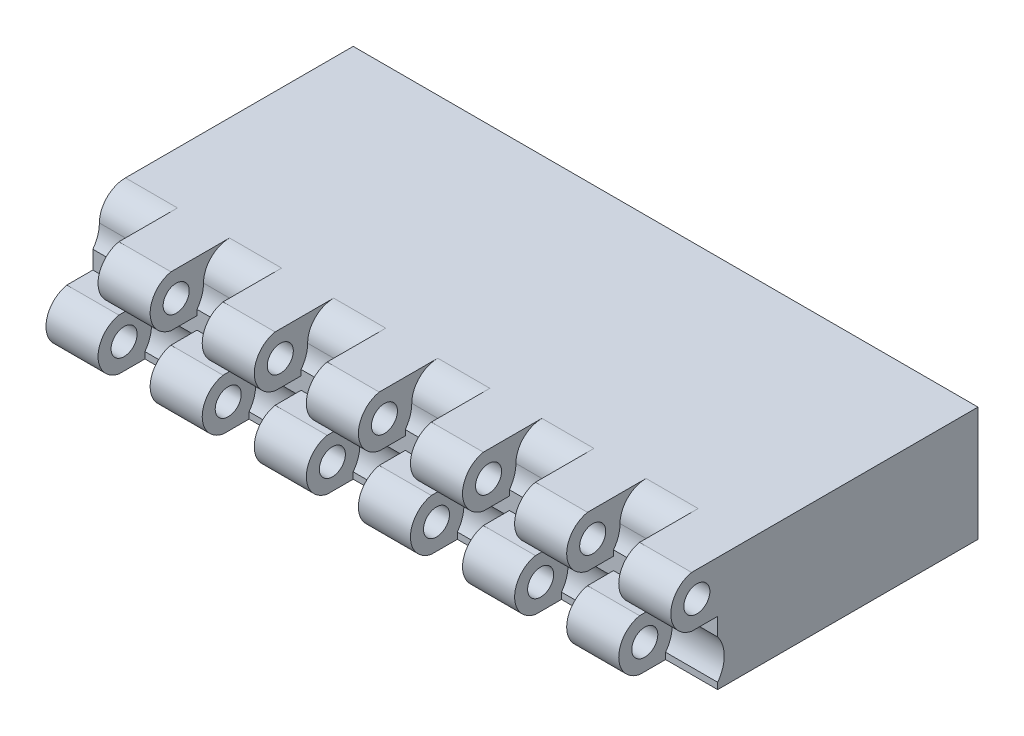
SolidWorks part; units mm, degrees
ref_plane "Front Plane" through (0, 0, 0) normal (0, 0, 1) x (1, 0, 0)
ref_plane "Top Plane" through (0, 0, 0) normal (0, 1, 0) x (1, 0, 0)
ref_plane "Right Plane" through (0, 0, 0) normal (1, 0, 0) x (0, 0, -1)
sketch "Sketch1" plane through (0, 0, 0) normal (1, 0, 0) x (0, 0, -1)
  line L1 (-25, 11) -> (25, 11)
  line L2 (-25, 11) -> (-25, -11)
  line L3 (-25, -11) -> (25, -11)
  line L4 (25, 11) -> (25, -11)
  line L5 (-25, 11) -> (25, -11) construction
  line L6 (-25, -11) -> (25, 11) construction
  point P0 (0, 0)
  dimension "D1" = 22
  dimension "D2" = 50
extrude "Boss-Extrude1" add sketch "Sketch1" along normal mid plane 120
sketch "Sketch5" plane through (60, 0, 0) normal (1, 0, 0) x (0, 0, -1)
  line L0 (-25, 11) -> (-25, 1.01) construction
  line L1 (-25, 11) -> (-25, -11) construction
  line L2 (-25, 6.005) -> (-30, 6.005) construction
  line L3 (-26.2433, 11) -> (-23.75, 11)
  line L4 (25, 11) -> (-25, 11) construction
  line L5 (-23.75, 11) -> (-23.75, 6.005)
  arc A1 (-26.2433, 11) -> (-23.75, 6.005) centre (-30, 6.005) ccw
extrude "Cut-Extrude2" cut sketch "Sketch5" against normal up to next
sketch "Sketch6" plane through (-60, 0, 0) normal (-1, 0, 0) x (0, 0, 1)
  line L0 (25, -11) -> (25, -1.01) construction
  line L1 (25, 2.255) -> (25, -11) construction
  line L2 (25, -6.005) -> (30, -6.005) construction
  circle A0 centre (30, -6.005) radius 6.26
  dimension "D1" = 9.99
extrude "Cut-Extrude3" cut sketch "Sketch6" against normal up to next
fillet "Fillet1" radius 5 1 edges at (0, 11, 23.75)
sketch "Sketch2" plane through (60, 0, 0) normal (1, 0, 0) x (0, 0, -1)
  line L0 (-30, 1.202) -> (-18.75, 1.202)
  line L1 (-25, -11) -> (-25, 1.202) construction
  line L13 (-18.75, 11) -> (-18.75, 1.202)
  line L14 (-30, 11) -> (-18.75, 11)
  arc A1 (-30, 11) -> (-30, 1.202) centre (-29, 6.101) ccw
  circle A2 centre (-29, 6.101) radius 2.5
  dimension "D3" = 5
  dimension "D1" = 2.5
  dimension "D2" = 11.25
extrude "Boss-Extrude2" add sketch "Sketch2" against normal blind 10
pattern_linear "LPattern1" count 6 spacing 20 along (-1, 0, 0) of "Boss-Extrude2"
sketch "Sketch3" plane through (-60, 0, 0) normal (-1, 0, 0) x (0, 0, 1)
  line L0 (23.75, -1.202) -> (30, -1.202)
  line L1 (30, -11) -> (23.75, -11)
  line L8 (23.75, -11) -> (23.75, -1.202)
  arc A1 (30, -11) -> (30, -1.202) centre (29, -6.101) ccw
  circle A2 centre (29, -6.101) radius 2.5
  point P7 (25, -0.3112)
  dimension "D2" = 4
  dimension "D3" = 5
  dimension "D4" = 2.5
  dimension "D1" = 6.25
extrude "Boss-Extrude3" add sketch "Sketch3" against normal blind 10 contours A1 A2 region at (-60, -1.3438, 26.875)
pattern_linear "LPattern2" count 6 spacing 20 along (1, 0, 0) of "Boss-Extrude3"
sketch "Sketch4" plane through (0, 0, -25) normal (0, 0, -1) x (-1, 0, 0)
  circle A0 centre (0, 0) radius 7
  dimension "D1" = 14
extrude "Cut-Extrude1" cut sketch "Sketch4" against normal blind 30
